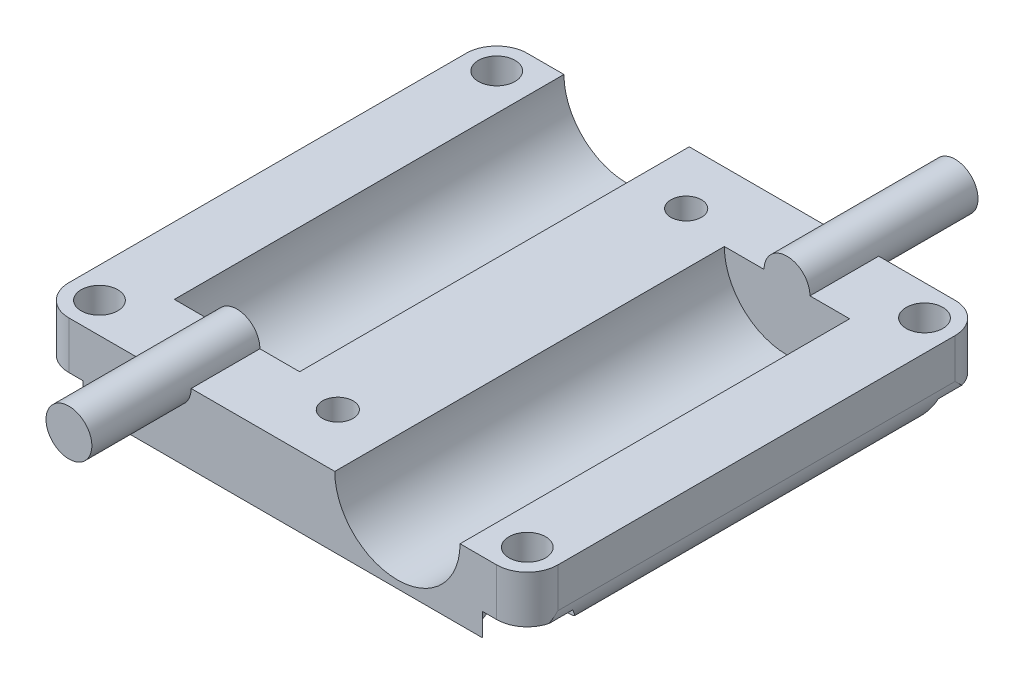
SolidWorks part; units mm, degrees
ref_plane "Front Plane" through (0, 0, 0) normal (0, 0, 1) x (1, 0, 0)
ref_plane "Top Plane" through (0, 0, 0) normal (0, 1, 0) x (1, 0, 0)
ref_plane "Right Plane" through (0, 0, 0) normal (1, 0, 0) x (0, 0, -1)
sketch "Sketch1" plane through (0, 0, 0) normal (0, 0, 1) x (1, 0, 0)
  line L1 (-12.0457, -6.5978) -> (19.9543, -6.5978)
  line L2 (-12.0457, -6.5978) -> (-12.0457, -0.0978)
  line L3 (-12.0457, -0.0978) -> (19.9543, -0.0978)
  line L4 (19.9543, -6.5978) -> (19.9543, -0.0978)
  dimension "D1" = 32
  dimension "D2" = 6.5
extrude "Boss-Extrude1" add sketch "Sketch1" along normal blind 30
fillet "Fillet1" radius 2 4 edges at (19.9543, -3.3478, 30) (-12.0457, -3.3478, 30) (-12.0457, -3.3478, 0) (19.9543, -3.3478, 0)
sketch "Sketch2" plane through (0, 0, 0) normal (0, 0, -1) x (-1, 0, 0)
  circle A0 centre (3.5457, -0.1978) radius 4.1
extrude "Cut-Extrude1" cut sketch "Sketch2" against normal blind 25.5
sketch "Sketch3" plane through (0, 0, 30) normal (0, 0, 1) x (1, 0, 0)
  circle A0 centre (11.4543, -0.1978) radius 4.1
extrude "Cut-Extrude2" cut sketch "Sketch3" against normal blind 25.5
sketch "Sketch5" plane through (0, 0, 30) normal (0, 0, 1) x (1, 0, 0)
  line L0 (19.9543, -0.0978) -> (19.9543, -6.5978) construction
  line L1 (-12.0457, -0.0978) -> (19.9543, -0.0978)
  line L2 (-12.0457, -0.0978) -> (-12.0457, -0.1978)
  line L3 (-12.0457, -0.1978) -> (19.9543, -0.1978)
  line L4 (19.9543, -0.0978) -> (19.9543, -0.1978)
  dimension "D1" = 0.1
extrude "Cut-Extrude3" cut sketch "Sketch5" against normal through all
sketch "Sketch6" plane through (0, 0, 30) normal (0, 0, 1) x (1, 0, 0)
  line L0 (-12.0457, -6.5978) -> (-12.0457, -0.1978) construction
  line L1 (19.9543, -6.5978) -> (-12.0457, -6.5978)
  line L2 (19.9543, -6.5978) -> (19.9543, -4.7978)
  line L3 (19.9543, -4.7978) -> (-12.0457, -4.7978)
  line L4 (-12.0457, -6.5978) -> (-12.0457, -4.7978)
  dimension "D1" = 1.8
extrude "Cut-Extrude4" cut sketch "Sketch6" against normal through all
sketch "Sketch7" plane through (0, -4.7978, 0) normal (0, -1, 0) x (1, 0, 0)
  circle A0 centre (-10.0457, 2) radius 2.2
  dimension "D1" = 4.4
extrude "Cut-Extrude5" cut sketch "Sketch7" against normal blind 1.5
sketch "Sketch8" plane through (0, -3.2978, 0) normal (0, -1, 0) x (1, 0, 0)
  circle A0 centre (-10.0457, 2) radius 1.2
  dimension "D1" = 2.4
extrude "Cut-Extrude6" cut sketch "Sketch8" against normal blind 4
sketch "Sketch9" plane through (0, -4.7978, 0) normal (0, -1, 0) x (1, 0, 0)
  circle A0 centre (-10.0457, 28) radius 1.2
  circle A1 centre (17.9543, 28) radius 1.2
  circle A2 centre (17.9543, 2) radius 1.2
  dimension "D1" = 2.4
  dimension "D2" = 2.4
  dimension "D3" = 2.4
extrude "Cut-Extrude7" cut sketch "Sketch9" against normal blind 6
sketch "Sketch10" plane through (0, -4.7978, 0) normal (0, -1, 0) x (1, 0, 0)
  circle A0 centre (-10.0457, 28) radius 2.2
  circle A1 centre (17.9543, 28) radius 2.2
  circle A2 centre (17.9543, 2) radius 2.2
  dimension "D1" = 4.4
  dimension "D2" = 4.4
  dimension "D3" = 4.4
extrude "Cut-Extrude8" cut sketch "Sketch10" against normal blind 1.5
sketch "Sketch11" plane through (0, -0.1978, 0) normal (0, 1, 0) x (1, 0, 0)
  circle A0 centre (3.9543, -3.6) radius 1
  circle A1 centre (3.9543, -26.4) radius 1
extrude "Cut-Extrude9" cut sketch "Sketch11" against normal through all
sketch "Sketch12" plane through (0, -4.7978, 0) normal (0, -1, 0) x (1, 0, 0)
  circle A0 centre (3.9543, 26.4) radius 1.7
  circle A1 centre (3.9543, 3.6) radius 1.7
  dimension "D1" = 3.4
  dimension "D2" = 3.4
extrude "Cut-Extrude10" cut sketch "Sketch12" against normal blind 1.5
sketch "Sketch14" plane through (0, 0, 4.5) normal (0, 0, 1) x (1, 0, 0)
  line L0 (7.3543, -0.1978) -> (15.5543, -0.1978) construction
  circle A0 centre (11.4543, -0.1978) radius 1.5
  dimension "D1" = 3
extrude "Boss-Extrude3" add sketch "Sketch14" against normal blind 11
sketch "Sketch15" plane through (0, 0, 25.5) normal (0, 0, -1) x (-1, 0, 0)
  line L0 (-0.5543, -0.1978) -> (7.6457, -0.1978) construction
  circle A0 centre (3.5457, -0.1978) radius 1.5
  dimension "D1" = 3
extrude "Boss-Extrude4" add sketch "Sketch15" against normal blind 11
fillet "Fillet2" radius 2 2 edges at (19.9543, -4.7978, 15) (-12.0457, -4.7978, 15)
